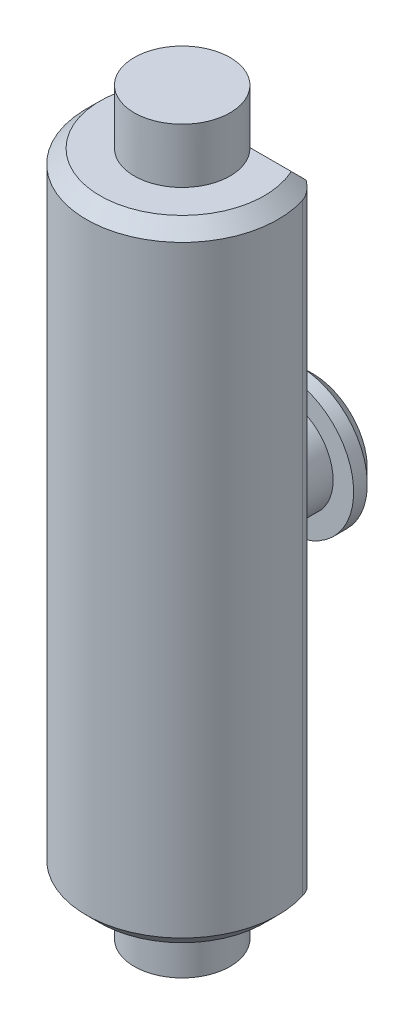
SolidWorks part; units mm, degrees
ref_plane "前视基准面" through (0, 0, 0) normal (0, 0, 1) x (1, 0, 0)
ref_plane "上视基准面" through (0, 0, 0) normal (0, 1, 0) x (1, 0, 0)
ref_plane "右视基准面" through (0, 0, 0) normal (1, 0, 0) x (0, 0, -1)
other "Configuration Table"
sketch "草图1" plane through (0, 0, 0) normal (0, 1, 0) x (1, 0, 0)
  line L0 (-3.0248, 1.7608) -> (3.0248, 1.7608)
  circle A1 centre (0, 0) radius 1.75 construction
  arc A2 (3.0248, 1.7608) -> (-3.0248, 1.7608) centre (0, 0) cw
  point P6 (0, 0)
  dimension "D1" = 3.5
  dimension "D2" = 3.5
extrude "凸台-拉伸1" add sketch "草图1" along normal blind 23
sketch "草图2" plane through (0, 23, 0) normal (0, 1, 0) x (1, 0, 0)
  circle A0 centre (0, 0) radius 1.75
  dimension "D1" = 3.5
extrude "凸台-拉伸2" add sketch "草图2" along normal blind 2
sketch "草图3" plane through (0, 0, 0) normal (0, -1, 0) x (1, 0, 0)
  circle A0 centre (0, 0) radius 1.75
  dimension "D1" = 3.5
extrude "凸台-拉伸3" add sketch "草图3" along normal blind 2
sketch "草图4" plane through (0, 0, -1.7608) normal (0, 0, -1) x (-1, 0, 0)
  line L0 (0, 23) -> (0, 0) construction
  line L2 (-3.0248, 23) -> (3.0248, 23) construction
  circle A0 centre (0, 11.5) radius 1.75
  dimension "D1" = 3.5
extrude "凸台-拉伸4" add sketch "草图4" along normal blind 2
sketch "草图5" plane through (0, 0, -3.7608) normal (0, 0, -1) x (-1, 0, 0)
  circle A0 centre (0, 11.5) radius 2.5
  dimension "D1" = 5
extrude "凸台-拉伸5" add sketch "草图5" along normal blind 1
chamfer "倒角1" distance 0.5 angle 45 1 edges at (-2.5, 11.5, -4.7608)
sketch "草图6" plane through (0, 0, -4.7608) normal (0, 0, -1) x (-1, 0, 0)
  circle A0 centre (0, 11.5) radius 0.75
  dimension "D1" = 1.5
extrude "切除-拉伸1" cut sketch "草图6" against normal blind 0.5 contours A0
chamfer "倒角2" distance 0.2 angle 45 1 edges at (-0.75, 11.5, -4.7608)
chamfer "倒角3" distance 0.5 angle 45 4 edges at (0, 0, -1.7608) (0, 0, 3.5) (0, 23, -1.7608) (0, 23, 3.5)
fillet "圆角3" radius 1 2 edges at (3.0248, 11.5, -1.7608) (-3.0248, 11.5, -1.7608)
